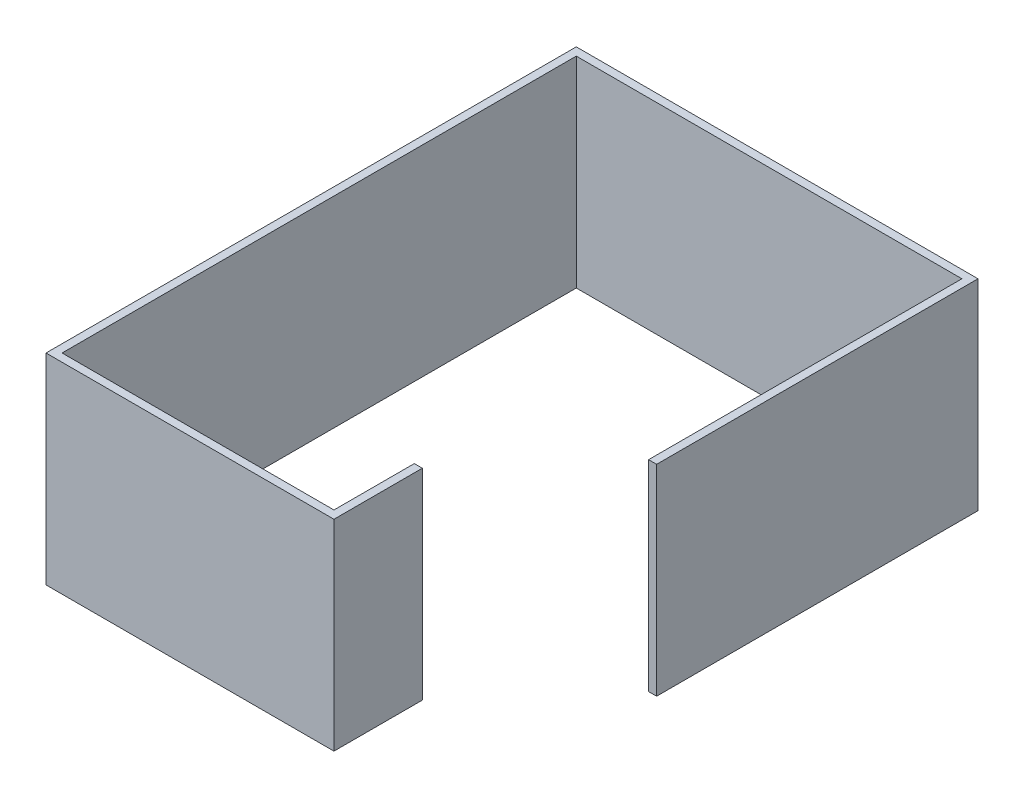
SolidWorks part; units mm, degrees
ref_plane "Front Plane" through (0, 0, 0) normal (0, 0, 1) x (1, 0, 0)
ref_plane "Top Plane" through (0, 0, 0) normal (0, 1, 0) x (1, 0, 0)
ref_plane "Right Plane" through (0, 0, 0) normal (1, 0, 0) x (0, 0, -1)
sketch "Sketch1" plane through (0, 0, 0) normal (0, 1, 0) x (1, 0, 0)
  line L0 (-250, 0) -> (-250, 500)
  line L1 (-250, 500) -> (250, 500)
  line L2 (250, 500) -> (250, 0)
  line L3 (250, 0) -> (240, 0)
  line L4 (240, 0) -> (240, 490)
  line L5 (240, 490) -> (-240, 490)
  line L6 (-240, 490) -> (-240, 0)
  line L7 (-240, 0) -> (-250, 0)
  dimension "D1" = 10
  dimension "D2" = 10
  dimension "D3" = 10
  dimension "D4" = 250
  dimension "D5" = 250
  dimension "D6" = 500
extrude "Boss-Extrude1" add sketch "Sketch1" along normal blind 250
sketch "Sketch3" plane through (0, 250, 0) normal (0, 1, 0) x (1, 0, 0)
  line L0 (250, 0) -> (250, 500) construction
  line L1 (240, 0) -> (250, 0)
  line L2 (240, 0) -> (240, 100)
  line L3 (240, 100) -> (250, 100)
  line L4 (250, 0) -> (250, 100)
  dimension "D1" = 100
extrude "Cut-Extrude1" cut sketch "Sketch3" against normal blind 250
sketch "Sketch4" plane through (0, 0, 0) normal (0, 0, 1) x (1, 0, 0)
  line L0 (-240, 0) -> (240, 0) construction
  line L1 (-250, 250) -> (-240, 250)
  line L2 (-250, 250) -> (-250, 0)
  line L3 (-250, 0) -> (-240, 0)
  line L4 (-240, 250) -> (-240, 0)
  line L5 (-240, 250) -> (-240, 0) construction
extrude "Boss-Extrude2" add sketch "Sketch4" along normal blind 160
sketch "Sketch5" plane through (-240, 0, 0) normal (1, 0, 0) x (0, 0, -1)
  line L0 (-160, 0) -> (490, 0) construction
  line L1 (-160, 250) -> (-150, 250)
  line L2 (-160, 250) -> (-160, 0)
  line L3 (-160, 0) -> (-150, 0)
  line L4 (-150, 250) -> (-150, 0)
  dimension "D1" = 10
extrude "Boss-Extrude3" add sketch "Sketch5" along normal blind 348.4
sketch "Sketch6" plane through (0, 0, 150) normal (0, 0, -1) x (-1, 0, 0)
  line L0 (-250, 0) -> (250, 0) construction
  line L1 (-108.4, 250) -> (-98.4, 250)
  line L2 (-108.4, 250) -> (-108.4, 0)
  line L3 (-108.4, 0) -> (-98.4, 0)
  line L4 (-98.4, 250) -> (-98.4, 0)
  dimension "D1" = 10
extrude "Boss-Extrude4" add sketch "Sketch6" along normal blind 100
